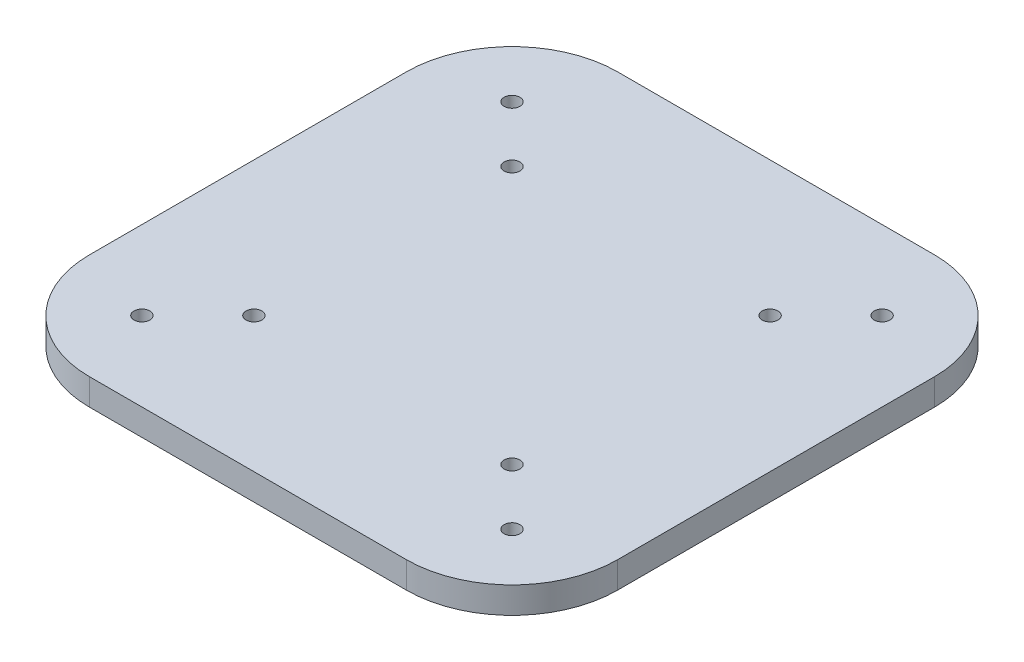
SolidWorks part; units mm, degrees
ref_plane "Front" through (0, 0, 0) normal (0, 0, 1) x (1, 0, 0)
ref_plane "Top" through (0, 0, 0) normal (0, 1, 0) x (1, 0, 0)
ref_plane "Right" through (0, 0, 0) normal (1, 0, 0) x (0, 0, -1)
sketch "Sketch1" plane through (0, 0, 0) normal (0, 1, 0) x (1, 0, 0)
  line L1 (-42.4365, 48.9848) -> (17.5635, 48.9848)
  line L2 (-62.4365, 28.9848) -> (-62.4365, -31.0152)
  line L3 (-42.4365, -51.0152) -> (17.5635, -51.0152)
  line L4 (37.5635, 28.9848) -> (37.5635, -31.0152)
  arc A0 (37.5635, -31.0152) -> (17.5635, -51.0152) centre (17.5635, -31.0152) cw
  arc A1 (-42.4365, -51.0152) -> (-62.4365, -31.0152) centre (-42.4365, -31.0152) cw
  arc A2 (-62.4365, 28.9848) -> (-42.4365, 48.9848) centre (-42.4365, 28.9848) cw
  arc A3 (37.5635, 28.9848) -> (17.5635, 48.9848) centre (17.5635, 28.9848) ccw
  point P6 (37.5635, -51.0152)
  point P9 (-62.4365, -51.0152)
  point P12 (-62.4365, 48.9848)
  dimension "D3" = 62.4365
  dimension "D4" = 48.9848
  dimension "D1" = 20
  dimension "D2" = 37.5635
extrude "Boss-Extrude1" add sketch "Sketch1" along normal blind 5
hole_wizard "Ø3.0 (3) Diameter Hole1" positions "Sketch3" profile "Sketch2" hole size "Ø3.0" standard "ANSI Metric" end condition through all
sketch "Sketch3" plane through (0, 5, 0) normal (0, 1, 0) x (1, 0, 0)
  line L0 (31.7056, -45.1574) -> (17.5635, -31.0152) construction
  line L2 (37.5635, -31.0152) -> (37.5635, 28.9848) construction
  arc A0 (17.5635, -51.0152) -> (37.5635, -31.0152) centre (17.5635, -31.0152) ccw construction
  point P0 (22.5635, -36.0152)
  dimension "D1" = 15
sketch "Sketch2" plane through (22.5635, 5, 36.0152) normal (1, 0, 0) x (0, 0, 1)
  line L0 (0, 0) -> (0, 5)
  line L1 (0, 5) -> (1.5, 5)
  line L2 (1.5, 5) -> (1.5, 0)
  line L5 (1.5, 0) -> (0, 0)
  line L11 (0, -6.35) -> (0, 107.95) construction
  dimension "Thru Hole Dia." = 3
  dimension "Thru Hole Depth" = 5
ref_axis "Axis3" through (-56.5787, 5, -43.1269) along (0.7071, 0, 0.7071)
pattern_linear "LPattern1 15mm" count 2 spacing 15 along (-0.7071, 0, -0.7071) of "Ø3.0 (3) Diameter Hole1"
ref_point "Point1"
ref_point "Point2"
ref_axis "Axis4" through (-12.4801, 46.0588, 0.9717) along (0, -1, 0)
ref_axis "Axis5" through (-56.5787, 5, 45.1574) along (0.7071, 0, -0.7071)
pattern_circular "CirPattern2" count 4 every 90 about axis through (-12.4801, 46.0588, 0.9717) along (0, -1, 0) of "LPattern1 15mm"
